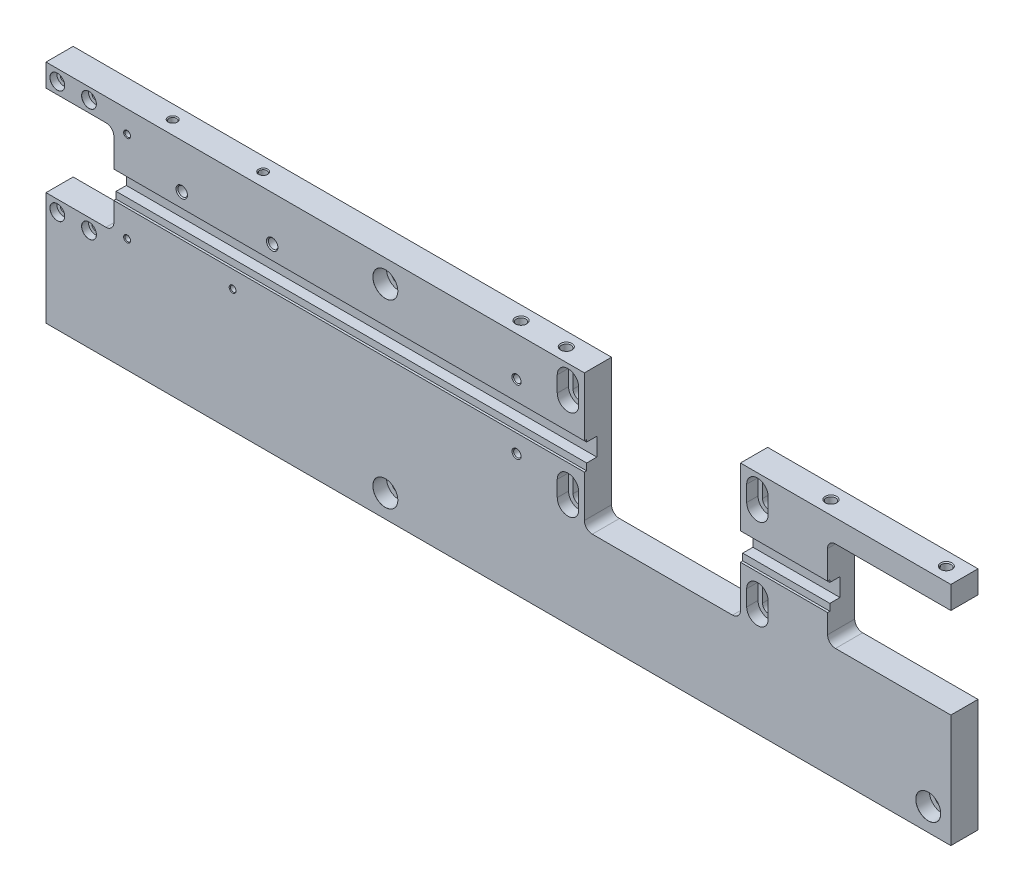
SolidWorks part; units mm, degrees
ref_plane "Front Plane" through (0, 0, 0) normal (0, 0, 1) x (1, 0, 0)
ref_plane "Top Plane" through (0, 0, 0) normal (0, 1, 0) x (1, 0, 0)
ref_plane "Right Plane" through (0, 0, 0) normal (1, 0, 0) x (0, 0, -1)
sketch "Sketch1" plane through (0, 0, 0) normal (0, 0, 1) x (1, 0, 0)
  line L1 (-200, -50) -> (200, -50)
  line L2 (-200, -50) -> (-200, 50)
  line L3 (-200, 50) -> (200, 50)
  line L4 (200, -50) -> (200, 50)
  line L5 (-200, -50) -> (200, 50) construction
  line L6 (-200, 50) -> (200, -50) construction
  point P0 (0, 0)
  dimension "D1" = 400
  dimension "D2" = 100
extrude "Base" add sketch "Sketch1" along normal blind 12
sketch "Sketch2" plane through (0, 0, 12) normal (0, 0, 1) x (1, 0, 0)
  line L0 (200, -50) -> (200, 50) construction
  line L1 (200, 0) -> (149, 0)
  line L2 (200, 0) -> (200, 40)
  line L3 (200, 40) -> (149, 40)
  line L4 (145.5, 3.5) -> (145.5, 36.5)
  line L5 (200, 50) -> (-200, 50) construction
  arc A0 (149, 0) -> (145.5, 3.5) centre (149, 3.5) cw
  arc A1 (149, 40) -> (145.5, 36.5) centre (149, 36.5) ccw
  dimension "D1" = 3.5
  dimension "D2" = 3.5
  dimension "D3" = 40
  dimension "D4" = 51
  dimension "D5" = 33
  dimension "D6" = 10
extrude "Part Tape Mover Cutout" cut sketch "Sketch2" against normal through all
sketch "Sketch3" plane through (0, 0, 12) normal (0, 0, 1) x (1, 0, 0)
  line L0 (200, 50) -> (-200, 50) construction
  line L1 (41.5, -10) -> (103.5, -10)
  line L2 (38, -6.5) -> (38, 50)
  line L3 (38, 50) -> (107, 50)
  line L4 (107, -6.5) -> (107, 50)
  line L5 (-200, -50) -> (200, -50) construction
  line L6 (200, -50) -> (200, 0) construction
  arc A0 (103.5, -10) -> (107, -6.5) centre (103.5, -6.5) ccw
  arc A1 (41.5, -10) -> (38, -6.5) centre (41.5, -6.5) cw
  point P9 (107, -10)
  point P12 (38, -10)
  dimension "D3" = 3.5
  dimension "D4" = 3.5
  dimension "D1" = 69
  dimension "D2" = 60
  dimension "D5" = 40
  dimension "D6" = 93
extrude "Press Plate Cutout" cut sketch "Sketch3" against normal through all
sketch "Sketch4" plane through (0, 0, 12) normal (0, 0, 1) x (1, 0, 0)
  line L0 (-200, 50) -> (-200, -50) construction
  line L1 (-200, 40) -> (-173.5, 40)
  line L2 (-200, 40) -> (-200, 0)
  line L3 (-200, 0) -> (-173.5, 0)
  line L4 (-170, 36.5) -> (-170, 3.5)
  line L5 (38, 50) -> (-200, 50) construction
  arc A0 (-173.5, 0) -> (-170, 3.5) centre (-173.5, 3.5) ccw
  arc A1 (-173.5, 40) -> (-170, 36.5) centre (-173.5, 36.5) cw
  dimension "D1" = 3.5
  dimension "D2" = 3.5
  dimension "D3" = 40
  dimension "D4" = 10
  dimension "D5" = 26.5
extrude "Roller Cutout" cut sketch "Sketch4" against normal through all
sketch "Sketch5" plane through (0, 0, 12) normal (0, 0, 1) x (1, 0, 0)
  line L0 (-170, 3.5) -> (-170, 36.5) construction
  line L1 (-170, 23) -> (145.5, 23)
  line L2 (-170, 23) -> (-170, 15)
  line L3 (-170, 15) -> (145.5, 15)
  line L4 (145.5, 23) -> (145.5, 15)
  line L5 (145.5, 36.5) -> (145.5, 3.5) construction
  line L6 (38, 50) -> (-200, 50) construction
  dimension "D1" = 8
  dimension "D2" = 27
extrude "Part Tape Cutout" cut sketch "Sketch5" against normal blind 5.5
sketch "Sketch6" plane through (0, 0, 12) normal (0, 0, 1) x (1, 0, 0)
  line L1 (-170, 24) -> (145.5, 24)
  line L2 (-170, 24) -> (-170, 12)
  line L3 (-170, 12) -> (145.5, 12)
  line L4 (145.5, 24) -> (145.5, 12)
  line L8 (-170, 3.5) -> (-170, 15) construction
  line L10 (-170, 15) -> (38, 15) construction
  line L11 (145.5, 15) -> (145.5, 3.5) construction
  dimension "D1" = 12
  dimension "D2" = 3
extrude "Part Tape Rest" cut sketch "Sketch6" against normal blind 1
hole_wizard "CBORE for M6 SHCS1" positions "Sketch15" profile "Sketch16" counterbore size "M6" standard "ANSI Metric" end condition through all
sketch "Sketch15" plane through (0, 0, 12) normal (0, 0, 1) x (1, 0, 0)
  line L0 (200, -50) -> (200, 0) construction
  line L2 (-200, -50) -> (200, -50) construction
  point P0 (190, -40)
  point P8 (-50, -40)
  point P10 (-50, 40)
  dimension "D1" = 10
  dimension "D2" = 10
  dimension "D3" = 240
  dimension "D4" = 80
sketch "Sketch16" plane through (190, -40, 12) normal (1, 0, 0) x (0, -1, 0)
  line L0 (0, 0) -> (0, 12)
  line L1 (0, 12) -> (3.3, 12)
  line L3 (3.3, 12) -> (3.3, 6)
  line L4 (5.5, 6) -> (3.3, 6)
  line L5 (5.5, 6) -> (5.5, 0.025)
  line L6 (5.5, 0.025) -> (5.525, 0)
  line L7 (5.525, 0) -> (0, 0)
  line L8 (-5.5, 0.025) -> (-5.525, 0) construction
  line L11 (0, -6.35) -> (0, 107.95) construction
  dimension "Thru Hole Dia." = 6.6
  dimension "Thru Hole Depth" = 12
  dimension "C'Bore Dia." = 11
  dimension "C'Bore Depth" = 6
  dimension "Near C'Sink Dia." = 11.05
  dimension "Near C'Sink Angle" = 90
hole_wizard "CBORE for M3 SHCS2" positions "Sketch17" profile "Sketch18" counterbore size "M3" standard "ANSI Metric" end condition through all
sketch "Sketch17" plane through (0, 0, 12) normal (0, 0, 1) x (1, 0, 0)
  line L0 (-173.5, 40) -> (-200, 40) construction
  line L1 (-200, 50) -> (-200, 40) construction
  point P0 (-195, 45)
  dimension "D1" = 5
  dimension "D2" = 5
sketch "Sketch18" plane through (-195, 45, 12) normal (1, 0, 0) x (0, -1, 0)
  line L0 (0, 0) -> (0, 12)
  line L1 (0, 12) -> (1.7, 12)
  line L3 (1.7, 12) -> (1.7, 3)
  line L4 (3.25, 3) -> (1.7, 3)
  line L5 (3.25, 3) -> (3.25, 0.025)
  line L6 (3.25, 0.025) -> (3.275, 0)
  line L7 (3.275, 0) -> (0, 0)
  line L8 (-3.25, 0.025) -> (-3.275, 0) construction
  line L11 (0, -6.35) -> (0, 107.95) construction
  dimension "Thru Hole Dia." = 3.4
  dimension "Thru Hole Depth" = 12
  dimension "C'Bore Dia." = 6.5
  dimension "C'Bore Depth" = 3
  dimension "Near C'Sink Dia." = 6.55
  dimension "Near C'Sink Angle" = 90
pattern_linear "LPattern2" count 2 spacing 14 along (1, 0, 0) count 2 spacing 50 along (0, -1, 0) of "CBORE for M3 SHCS2"
hole_wizard "M5x0.8 Tapped Hole1" positions "Sketch19" profile "Sketch20" tap size "M5x0.8" standard "ANSI Metric"
sketch "Sketch19" plane through (0, 50, 0) normal (0, 1, 0) x (1, 0, 0)
  line L0 (200, -12) -> (200, 0) construction
  line L1 (200, 0) -> (200, -12) construction
  line L2 (38, 0) -> (38, -12) construction
  point P0 (192, -6)
  point P2 (141, -6)
  point P14 (200, -6)
  point P16 (24, -6)
  point P18 (4, -6)
  dimension "D1" = 8
  dimension "D2" = 51
  dimension "D3" = 14
  dimension "D4" = 20
cosmetic thread "Hole Thread1" parameters "D1"=10, "D2"=5
cosmetic thread "Hole Thread2" parameters "D1"=10, "D2"=5
sketch "Sketch20" plane through (192, 50, 6) normal (1, 0, 0) x (0, 0, 1)
  line L0 (0, 0) -> (0, 11.2618)
  line L1 (0, 11.2618) -> (2.1, 10)
  line L2 (2.1, 10) -> (2.1, 0.425)
  line L3 (2.1, 0.425) -> (2.525, 0)
  line L5 (2.525, 0) -> (0, 0)
  line L6 (-2.1, 0.425) -> (-2.525, 0) construction
  line L10 (0, 11.2618) -> (-2.1, 10) construction
  line L11 (0, -6.35) -> (0, 107.95) construction
  dimension "Tap Drill Dia." = 4.2
  dimension "Tap Drill Depth" = 10
  dimension "Near C'Sink Dia." = 5.05
  dimension "Near C'Sink Angle" = 90
  dimension "Drill Angle" = 118
cosmetic thread "Hole Thread3" parameters "D1"=10, "D2"=5
cosmetic thread "Hole Thread4" parameters "D1"=10, "D2"=5
hole_wizard "M4x0.7 Tapped Hole1" positions "Sketch23" profile "Sketch24" tap size "M4x0.7" standard "ANSI Metric"
sketch "Sketch23" plane through (0, 50, 0) normal (0, 1, 0) x (1, 0, 0)
  line L0 (-200, -12) -> (-200, 0) construction
  line L1 (-200, 0) -> (-200, -12) construction
  point P0 (-150, -6)
  point P2 (-110, -6)
  point P14 (-200, -6)
  dimension "D1" = 40
  dimension "D2" = 50
sketch "Sketch24" plane through (-150, 50, 6) normal (1, 0, 0) x (0, 0, 1)
  line L0 (0, 0) -> (0, 11.0914)
  line L1 (0, 11.0914) -> (1.65, 10.1)
  line L2 (1.65, 10.1) -> (1.65, 0.375)
  line L3 (1.65, 0.375) -> (2.025, 0)
  line L5 (2.025, 0) -> (0, 0)
  line L6 (-1.65, 0.375) -> (-2.025, 0) construction
  line L10 (0, 11.0914) -> (-1.65, 10.1) construction
  line L11 (0, -6.35) -> (0, 107.95) construction
  dimension "Tap Drill Dia." = 3.3
  dimension "Tap Drill Depth" = 10.1
  dimension "Near C'Sink Dia." = 4.05
  dimension "Near C'Sink Angle" = 90
  dimension "Drill Angle" = 118
cosmetic thread "Hole Thread5" parameters "D1"=8, "D2"=4
cosmetic thread "Hole Thread6" parameters "D1"=8, "D2"=4
hole_wizard "M3x0.5 Tapped Hole1" positions "Sketch27" profile "Sketch28" tap size "M3x0.5" standard "ANSI Metric" end condition through all
sketch "Sketch27" plane through (0, 0, 12) normal (0, 0, 1) x (1, 0, 0)
  line L0 (-170, 24) -> (-170, 36.5) construction
  line L2 (38, 24) -> (-170, 24) construction
  line L3 (-170, 12) -> (38, 12) construction
  line L4 (-170, 3.5) -> (-170, 12) construction
  point P0 (-164.15, 40.25)
  point P4 (-117.5, 4.3)
  point P6 (-164.15, 0.25)
  dimension "D1" = 5.85
  dimension "D2" = 16.25
  dimension "D3" = 40
  dimension "D4" = 7.7
  dimension "D5" = 52.5
sketch "Sketch28" plane through (-164.15, 40.25, 12) normal (1, 0, 0) x (0, -1, 0)
  line L0 (0, 0) -> (0, 12)
  line L1 (0, 12) -> (1.25, 12)
  line L2 (1.25, 12) -> (1.25, 0.275)
  line L3 (1.25, 0.275) -> (1.525, 0)
  line L5 (1.525, 0) -> (0, 0)
  line L6 (-1.25, 0.275) -> (-1.525, 0) construction
  line L11 (0, -6.35) -> (0, 107.95) construction
  dimension "Thru Tap Drill Dia." = 2.5
  dimension "Thru Tap Drill Depth" = 12
  dimension "Near C'Sink Dia." = 3.05
  dimension "Near C'Sink Angle" = 90
cosmetic thread "Hole Thread7" parameters "D2"=3
cosmetic thread "Hole Thread8" parameters "D2"=3
cosmetic thread "Hole Thread9" parameters "D2"=3
hole_wizard "M5x0.8 Tapped Hole2" positions "Sketch29" profile "Sketch30" tap size "M5x0.8" standard "ANSI Metric" end condition through all
sketch "Sketch29" plane through (0, 0, 12) normal (0, 0, 1) x (1, 0, 0)
  line L0 (-170, 24) -> (-170, 36.5) construction
  line L1 (38, 24) -> (-170, 24) construction
  point P0 (-140, 30.25)
  point P2 (-100, 30.25)
  dimension "D1" = 40
  dimension "D2" = 30
  dimension "D3" = 6.25
sketch "Sketch30" plane through (-140, 30.25, 12) normal (1, 0, 0) x (0, -1, 0)
  line L0 (0, 0) -> (0, 12)
  line L1 (0, 12) -> (2.1, 12)
  line L2 (2.1, 12) -> (2.1, 0.425)
  line L3 (2.1, 0.425) -> (2.525, 0)
  line L5 (2.525, 0) -> (0, 0)
  line L6 (-2.1, 0.425) -> (-2.525, 0) construction
  line L11 (0, -6.35) -> (0, 107.95) construction
  dimension "Thru Tap Drill Dia." = 4.2
  dimension "Thru Tap Drill Depth" = 12
  dimension "Near C'Sink Dia." = 5.05
  dimension "Near C'Sink Angle" = 90
cosmetic thread "Hole Thread10" parameters "D2"=5
cosmetic thread "Hole Thread11" parameters "D2"=5
hole_wizard "M4x0.7 Tapped Hole2" positions "Sketch31" profile "Sketch32" tap size "M4x0.7" standard "ANSI Metric" end condition through all
sketch "Sketch31" plane through (0, 0, 12) normal (0, 0, 1) x (1, 0, 0)
  line L0 (38, 50) -> (38, 24) construction
  line L1 (38, 50) -> (-200, 50) construction
  point P0 (8, 32.5)
  point P2 (8, 4)
  dimension "D1" = 30
  dimension "D2" = 17.5
  dimension "D3" = 28.5
sketch "Sketch32" plane through (8, 32.5, 12) normal (1, 0, 0) x (0, -1, 0)
  line L0 (0, 0) -> (0, 12)
  line L1 (0, 12) -> (1.65, 12)
  line L2 (1.65, 12) -> (1.65, 0.375)
  line L3 (1.65, 0.375) -> (2.025, 0)
  line L5 (2.025, 0) -> (0, 0)
  line L6 (-1.65, 0.375) -> (-2.025, 0) construction
  line L11 (0, -6.35) -> (0, 107.95) construction
  dimension "Thru Tap Drill Dia." = 3.3
  dimension "Thru Tap Drill Depth" = 12
  dimension "Near C'Sink Dia." = 4.05
  dimension "Near C'Sink Angle" = 90
cosmetic thread "Hole Thread12" parameters "D2"=4
cosmetic thread "Hole Thread13" parameters "D2"=4
hole_wizard "CBORE SLOT for M5 SHCS2" positions "Sketch35" profile "Sketch36" size "M5" standard "ANSI Metric" slot yes end condition through all
sketch "Sketch35" plane through (0, 0, 12) normal (0, 0, 1) x (1, 0, 0)
  line L0 (114.5, 33.5) -> (114.5, 46) construction
  line L1 (107, 24) -> (107, 50) construction
  line L2 (200, 50) -> (107, 50) construction
  point P0 (114.5, 39.75)
  point P7 (114.9114, 35.8278)
  dimension "D1" = 12.5
  dimension "D2" = 7.5
  dimension "D3" = 4
sketch "Sketch36" plane through (114.5, 39.75, 12) normal (1, 0, 0) x (0, -1, 0)
  line L0 (0, 0) -> (0, 12)
  line L1 (0, 12) -> (2.75, 12)
  line L3 (2.75, 12) -> (2.75, 5)
  line L4 (2.75, 5) -> (4.75, 5)
  line L5 (4.75, 5) -> (4.75, 0)
  line L7 (4.75, 0) -> (0, 0)
  line L11 (0, -6.35) -> (0, 107.95) construction
  dimension "Thru Hole Dia." = 5.5
  dimension "Thru Hole Depth" = 12
  dimension "C'Bore Dia." = 9.5
  dimension "C'Bore Depth" = 5
pattern_linear "LPattern3" count 2 spacing 83.75 along (-1, 0, 0) count 2 spacing 40 along (0, -1, 0) of "CBORE SLOT for M5 SHCS2"
